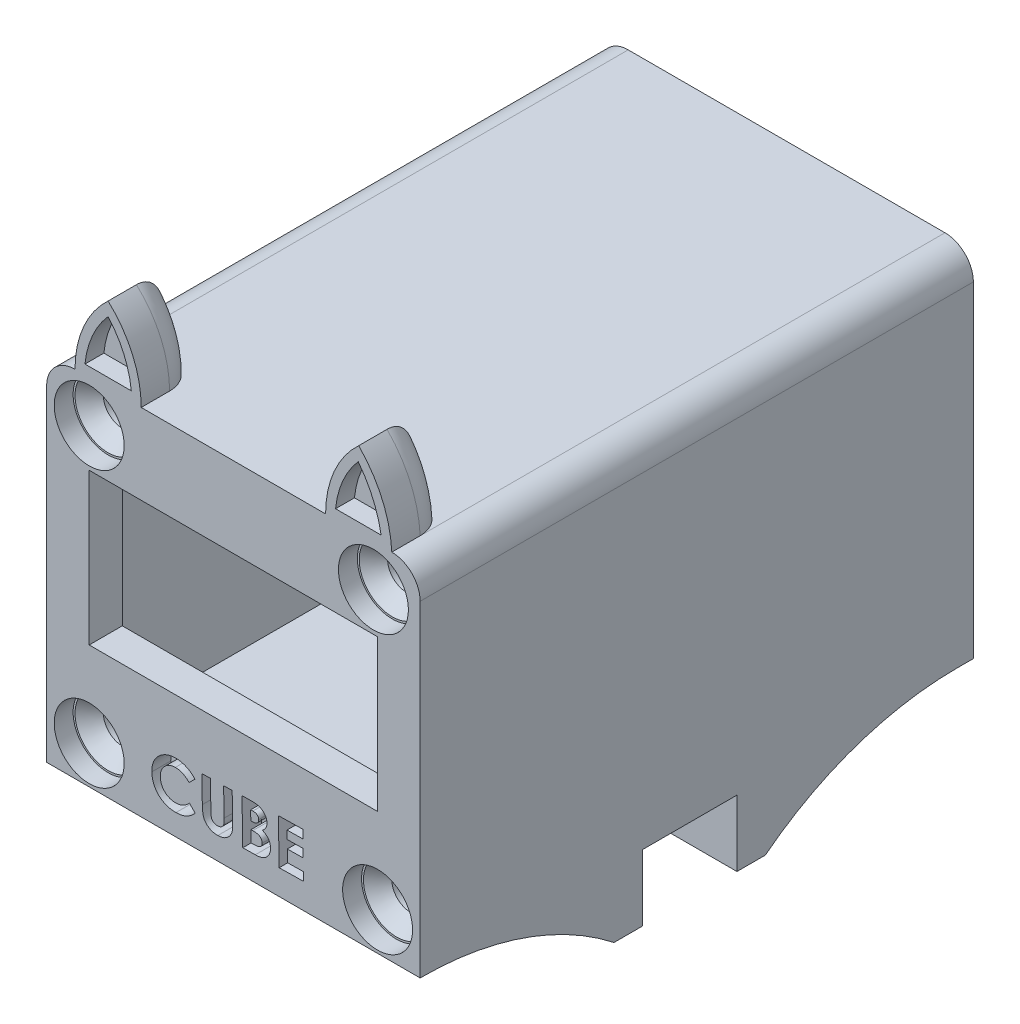
SolidWorks part; units mm, degrees
ref_plane "Plan de face" through (0, 0, 0) normal (0, 0, 1) x (1, 0, 0)
ref_plane "Plan de dessus" through (0, 0, 0) normal (0, 1, 0) x (1, 0, 0)
ref_plane "Plan de droite" through (0, 0, 0) normal (1, 0, 0) x (0, 0, -1)
sketch "Esquisse1" plane through (0, 0, 0) normal (0, 0, 1) x (1, 0, 0)
  line L0 (-17.8827, 11.8632) -> (15.6173, 11.8632)
  line L1 (-20.8827, 8.8632) -> (-20.8827, -25.6368)
  line L2 (18.6173, 8.8632) -> (18.6173, -25.6368)
  line L3 (-20.8827, -25.6368) -> (18.6173, -25.6368)
  line L5 (-16.3827, 3.3632) -> (14.1173, 3.3632)
  line L6 (-16.3827, 3.3632) -> (-16.3827, -12.6368)
  line L7 (-16.3827, -12.6368) -> (14.1173, -12.6368)
  line L8 (14.1173, 3.3632) -> (14.1173, -12.6368)
  arc A0 (18.6173, 8.8632) -> (15.6173, 11.8632) centre (15.6173, 8.8632) ccw
  arc A1 (-20.8827, 8.8632) -> (-17.8827, 11.8632) centre (-17.8827, 8.8632) cw
  point P6 (18.6173, 11.8632)
  point P9 (-20.8827, 11.8632)
  dimension "D3" = 3
  dimension "D1" = 39.5
  dimension "D2" = 37.5
  dimension "D4" = 8.5
  dimension "D5" = 4.5
  dimension "D6" = 16
  dimension "D7" = 4.5
extrude "Boss.-Extru.1" add sketch "Esquisse1" along normal blind 3.5
sketch "Esquisse2" plane through (0, 0, 0) normal (0, 0, -1) x (-1, 0, 0)
  line L8 (-17.1173, 8.8632) -> (-17.1173, -24.1368)
  line L9 (-17.1173, -24.1368) -> (19.3827, -24.1368)
  line L10 (19.3827, -24.1368) -> (19.3827, 8.8632)
  line L11 (17.8827, 10.3632) -> (-15.6173, 10.3632)
  line L12 (-17.1173, 8.8632) -> (-17.1173, -24.1368)
  line L13 (-17.1173, -24.1368) -> (19.3827, -24.1368)
  line L14 (19.3827, -24.1368) -> (19.3827, 8.8632)
  line L15 (17.8827, 10.3632) -> (-15.6173, 10.3632)
  line L20 (-18.6173, 8.8632) -> (-18.6173, -25.6368)
  line L21 (-18.6173, -25.6368) -> (20.8827, -25.6368)
  line L22 (20.8827, -25.6368) -> (20.8827, 8.8632)
  line L23 (17.8827, 11.8632) -> (-15.6173, 11.8632)
  line L24 (-18.6173, 8.8632) -> (-18.6173, -25.6368)
  line L25 (-18.6173, -25.6368) -> (20.8827, -25.6368)
  line L26 (20.8827, -25.6368) -> (20.8827, 8.8632)
  line L27 (17.8827, 11.8632) -> (-15.6173, 11.8632)
  arc A4 (-15.6173, 10.3632) -> (-17.1173, 8.8632) centre (-15.6173, 8.8632) ccw
  arc A5 (19.3827, 8.8632) -> (17.8827, 10.3632) centre (17.8827, 8.8632) ccw
  arc A6 (-15.6173, 10.3632) -> (-17.1173, 8.8632) centre (-15.6173, 8.8632) ccw
  arc A7 (19.3827, 8.8632) -> (17.8827, 10.3632) centre (17.8827, 8.8632) ccw
  arc A10 (-15.6173, 11.8632) -> (-18.6173, 8.8632) centre (-15.6173, 8.8632) ccw
  arc A11 (20.8827, 8.8632) -> (17.8827, 11.8632) centre (17.8827, 8.8632) ccw
  arc A12 (-15.6173, 11.8632) -> (-18.6173, 8.8632) centre (-15.6173, 8.8632) ccw
  arc A13 (20.8827, 8.8632) -> (17.8827, 11.8632) centre (17.8827, 8.8632) ccw
  dimension "D1" = 1.5
  dimension "D2" = 0
extrude "Boss.-Extru.2" add sketch "Esquisse2" along normal blind 55
sketch "Esquisse3" plane through (0, 0, 0) normal (0, 0, -1) x (-1, 0, 0)
  line L0 (-17.1173, -24.1368) -> (19.3827, -24.1368) construction
  line L1 (-17.1173, -24.1368) -> (19.3827, -24.1368)
  line L2 (-17.1173, -24.1368) -> (-17.1173, -19.1368)
  line L3 (-17.1173, -19.1368) -> (19.3827, -19.1368)
  line L4 (19.3827, -24.1368) -> (19.3827, -19.1368)
  line L5 (-17.1173, -24.1368) -> (19.3827, -24.1368) construction
  line L6 (19.3827, -24.1368) -> (19.3827, 8.8632) construction
  line L7 (17.8827, 10.3632) -> (-15.6173, 10.3632) construction
  line L8 (-17.1173, 10.3632) -> (19.3827, 10.3632)
  line L9 (-17.1173, 10.3632) -> (-17.1173, 5.3632)
  line L10 (-17.1173, 5.3632) -> (19.3827, 5.3632)
  line L11 (19.3827, 10.3632) -> (19.3827, 5.3632)
  line L12 (-17.1173, 8.8632) -> (-17.1173, -24.1368) construction
  line L13 (-5.1173, -19.1368) -> (7.3827, -19.1368)
  line L14 (-5.1173, -19.1368) -> (-5.1173, -21.6368)
  line L15 (-5.1173, -21.6368) -> (7.3827, -21.6368)
  line L16 (7.3827, -19.1368) -> (7.3827, -21.6368)
  line L17 (-5.1173, 10.3632) -> (7.3827, 10.3632)
  line L18 (-5.1173, 10.3632) -> (-5.1173, 5.3632)
  line L19 (-5.1173, 5.3632) -> (7.3827, 5.3632)
  line L20 (7.3827, 10.3632) -> (7.3827, 5.3632)
  line M10 (17.8827, 10.3632) -> (-15.6173, 10.3632)
  arc M11 (-15.6173, 10.3632) -> (-17.1173, 8.8632) centre (-15.6173, 8.8632) ccw
  line M12 (-17.1173, 8.8632) -> (-17.1173, -24.1368)
  line M13 (-17.1173, -24.1368) -> (19.3827, -24.1368)
  line M14 (19.3827, -24.1368) -> (19.3827, 8.8632)
  arc M15 (19.3827, 8.8632) -> (17.8827, 10.3632) centre (17.8827, 8.8632) ccw
  dimension "D1" = 5
  dimension "D2" = 0
  dimension "D3" = 5
  dimension "D4" = 2.5
  dimension "D5" = 12
  dimension "D6" = 12
  dimension "D7" = 12
  dimension "D8" = 12
  dimension "D9" = 0
  dimension "D10" = 0
extrude "Boss.-Extru.3" add sketch "Esquisse3" along normal blind 1.5 contours L18 L10 M10 M11 M12 | L20 L10 M10 M14 M15 | L3 L16 L15 L14 M12 M13 M14 region at (-1.1327, -21.8951, 0) region at (11.0713, 7.8456, 0) region at (-13.3367, 7.8456, 0)
fillet "Congé1" radius 2.5 1 edges at (-1.1327, -21.6368, -1.5)
sketch "Esquisse4" plane through (0, 0, 3.5) normal (0, 0, 1) x (1, 0, 0)
  line L0 (-20.8827, 7.4632) -> (18.6173, 7.4632) construction
  line L1 (-20.8827, 8.8632) -> (-20.8827, -25.6368) construction
  line L2 (18.6173, -25.6368) -> (18.6173, 8.8632) construction
  line L4 (-20.8827, -25.6368) -> (18.6173, -25.6368) construction
  line L5 (14.1173, -25.6368) -> (14.1173, 11.8632) construction
  line L6 (15.6173, 11.8632) -> (-17.8827, 11.8632) construction
  line L8 (-16.3827, -25.6368) -> (-16.3827, 11.8632) construction
  line L10 (-20.8827, -21.6368) -> (18.6173, -21.6368) construction
  circle A0 centre (-16.3827, 7.4632) radius 2
  circle A1 centre (13.6721, 7.4632) radius 2
  circle A2 centre (14.1173, -21.6368) radius 2
  circle A3 centre (-16.3827, -21.6368) radius 2
  point P6 (-16.3827, 7.4632)
  point P17 (13.6721, 7.4632)
  point P18 (14.1173, -21.6368)
  point P19 (-16.3827, -21.6368)
  dimension "D5" = 4
  dimension "D6" = 4
  dimension "D7" = 4
  dimension "D8" = 4
  dimension "D1" = 4
  dimension "D2" = 4.5
  dimension "D3" = 4.4
  dimension "D4" = 4.5
extrude "Enlèv. mat.-Extru.1" cut sketch "Esquisse4" against normal blind 9.5
sketch "Esquisse5" plane through (0, 0, 3.5) normal (0, 0, 1) x (1, 0, 0)
  line L0 (-15.5568, -23.4583) -> (12.4785, -22.7833) construction
  circle A0 centre (-16.3827, -21.6368) radius 3.7
  circle A1 centre (13.6721, 7.4632) radius 3.7
  circle A2 centre (-16.3827, 7.4632) radius 3.7
  circle A3 centre (14.1173, -21.6368) radius 3.7
  circle A4 centre (-16.3827, -21.6368) radius 2 construction
  circle A5 centre (14.1173, -21.6368) radius 2 construction
  text T0 "<b>CUBE</b>" font "Century Gothic" height in points 18
  dimension "D1" = 7.4
  dimension "D2" = 7.4
  dimension "D3" = 7.4
  dimension "D4" = 7.4
extrude "Enlèv. mat.-Extru.5" cut sketch "Esquisse5" against normal blind 2
sketch "Esquisse6" plane through (0, 0, -55) normal (0, 0, -1) x (-1, 0, 0)
  line L0 (1.1327, 10.3632) -> (1.1327, -24.1368) construction
  line L1 (7.3827, 10.3632) -> (-5.1173, 10.3632) construction
  line L2 (-17.1173, -24.1368) -> (19.3827, -24.1368) construction
  line L3 (-2.6173, 8.1132) -> (-2.6173, 10.3632)
  line L4 (17.8827, 10.3632) -> (-15.6173, 10.3632) construction
  line L5 (-2.6173, 10.3632) -> (-2.6173, 11.8632)
  line L6 (4.8827, 8.1132) -> (4.8827, 10.3632)
  line L7 (1.1327, -6.8868) -> (9.6914, -6.8868) construction
  line L8 (4.8827, -21.8868) -> (4.8827, -24.1368)
  line L9 (-2.6173, -24.1368) -> (4.8827, -24.1368)
  line L10 (-2.6173, -21.8868) -> (-2.6173, -24.1368)
  line L11 (17.8827, 11.8632) -> (-15.6173, 11.8632) construction
  line L12 (-2.6173, 11.8632) -> (4.8827, 11.8632)
  line L13 (4.8827, 11.8632) -> (4.8827, 10.3632)
  line L14 (4.8827, -24.1368) -> (4.8827, -25.6368)
  line L15 (-18.6173, -25.6368) -> (20.8827, -25.6368) construction
  line L16 (4.8827, -25.6368) -> (-2.6173, -25.6368)
  line L17 (-2.6173, -25.6368) -> (-2.6173, -24.1368)
  circle A0 centre (1.1327, 8.1132) radius 2.25
  circle A1 centre (1.1327, 8.1132) radius 3.75
  circle A2 centre (1.1327, -21.8868) radius 3.75
  circle A3 centre (1.1327, -21.8868) radius 2.25
  point P31 (1.1327, 11.8632)
  line M6 (-18.6173, -25.6368) -> (20.8827, -25.6368)
  line M9 (17.8827, 11.8632) -> (-15.6173, 11.8632)
  line M12 (-15.6173, 10.3632) -> (17.8827, 10.3632)
  line M15 (19.3827, -24.1368) -> (-17.1173, -24.1368)
  dimension "D1" = 4.5
  dimension "D2" = 3.75
extrude "Boss.-Extru.5" add sketch "Esquisse6" against normal blind 7 contours A2 L10 M15 | A2 L17 M6 M15 | A2 L16 L14 M15 | A2 L9 M15 | L8 A2 M15 | A3 L9 A2 M15 | A1 A0 M12 | A1 L12 L5 M12 | A1 L3 M12 | A1 M12 | A1 L13 M12 M9 | A1 L6 M12 region at (2.3337, 9.2686, -55) region at (2.3968, 9.8125, -55) region at (1.6458, 11.2886, -55) region at (-4.6622, 9.8125, -55) region at (-1.1327, 10.9748, -55) region at (-3.9112, 11.2886, -55) region at (-4.5991, -23.0423, -55) region at (-4.6622, -23.5862, -55) region at (-3.9112, -25.0623, -55) region at (2.3968, -23.5862, -55) region at (-1.1327, -24.7485, -55) region at (1.6458, -25.0623, -55)
sketch "Esquisse7" plane through (0, 0, -55) normal (0, 0, -1) x (-1, 0, 0)
  line L0 (7.3827, 10.3632) -> (-5.1173, 10.3632) construction
  line L1 (-3.1173, 10.3632) -> (5.3827, 10.3632)
  line L2 (-3.1173, 10.3632) -> (-3.1173, 8.1132)
  line L3 (-3.1173, 8.1132) -> (5.3827, 8.1132)
  line L4 (5.3827, 10.3632) -> (5.3827, 8.1132)
  line L5 (-2.6173, 8.1132) -> (-2.6173, 10.3632) construction
  line L6 (4.8827, 8.1132) -> (4.8827, 10.3632) construction
  arc A0 (-3.1173, 8.1132) -> (5.3827, 8.1132) centre (1.1327, 8.1132) ccw
  arc A1 (4.8827, 8.1132) -> (-2.6173, 8.1132) centre (1.1327, 8.1132) cw
  line M13 (4.8827, 8.1132) -> (4.8827, 10.3632)
  line M14 (4.8827, 10.3632) -> (17.8827, 10.3632)
  line M24 (-15.6173, 10.3632) -> (-2.6173, 10.3632)
  line M25 (-2.6173, 10.3632) -> (-2.6173, 8.1132)
  arc M26 (-2.6173, 8.1132) -> (4.8827, 8.1132) centre (1.1327, 8.1132) ccw
  dimension "D1" = 2.25
  dimension "D2" = 0.5
  dimension "D3" = 0.5
extrude "Boss.-Extru.6" add sketch "Esquisse7" against normal blind 7 contours L3 A0 M26 | L4 L3 M14 M13 | L2 L3 M25 M24 region at (2.8673, 9.2382, -55) region at (2.8673, 8.0181, -55) region at (-5.1327, 9.2382, -55)
chamfer "Chanfrein1" distance 1.5 angle 45 4 edges at (-14.3827, -21.6368, 1.5) (-14.3827, 7.4632, 1.5) (15.6721, 7.4632, 1.5) (16.1173, -21.6368, 1.5)
sketch "Esquisse8" plane through (0, 0, 0) normal (0, 0, -1) x (-1, 0, 0)
  line L0 (7.3827, 10.3632) -> (7.3827, 5.3632) construction
  line L1 (-5.1173, 5.3632) -> (7.3827, 5.3632)
  line L2 (-5.1173, 5.3632) -> (-5.1173, 10.3632)
  line L3 (-5.1173, 10.3632) -> (7.3827, 10.3632)
  line L4 (7.3827, 5.3632) -> (7.3827, 10.3632)
  line L5 (7.3827, 10.3632) -> (7.3827, 5.3632) construction
extrude "Enlèv. mat.-Extru.6" cut sketch "Esquisse8" against normal blind 2
sketch "Esquisse10" plane through (0, 0, 3.5) normal (0, 0, 1) x (1, 0, 0)
  line L0 (-17.8827, 11.8632) -> (15.6173, 11.8632)
  line L1 (15.6173, 11.8632) -> (-17.8827, 11.8632) construction
  line L2 (-14.3827, 11.8632) -> (-14.3827, 19.8632) construction
  line L3 (-14.3827, 19.8632) -> (12.1173, 19.8632) construction
  line L4 (12.1173, 19.8632) -> (12.1173, 11.8632) construction
  line L5 (-14.3827, 11.8632) -> (-10.8827, 11.8632) construction
  line L6 (12.1173, 11.8632) -> (8.6173, 11.8632) construction
  arc A0 (18.6173, 8.8632) -> (15.6173, 11.8632) centre (15.6173, 8.8632) ccw construction
  arc A1 (-17.8827, 11.8632) -> (-14.3827, 19.8632) centre (-6.9898, 11.8632) cw
  arc A2 (-10.8827, 11.8632) -> (-14.3827, 19.8632) centre (-21.7756, 11.8632) ccw
  arc A3 (8.6173, 11.8632) -> (12.1173, 19.8632) centre (19.5102, 11.8632) cw
  arc A4 (12.1173, 19.8632) -> (15.6173, 11.8632) centre (3.4155, 11.2905) cw
  dimension "D1" = 3.5
  dimension "D2" = 3.5
  dimension "D3" = 8
  dimension "D4" = 3.5
  dimension "D5" = 3.5
extrude "Boss.-Extru.7" add sketch "Esquisse10" against normal blind 6 contours A4 A3 L0 | L0 A2 A1 region at (-14.3827, 14.9398, 3.5) region at (12.0777, 14.9199, 3.5)
fillet "Congé2" radius 3 4 edges at (14.6066, 16.1866, -2.5) (9.5306, 16.2292, -2.5) (-11.796, 16.2292, -2.5) (-16.9694, 16.2292, -2.5)
sketch "Esquisse12" plane through (0, 0, 3.5) normal (0, 0, 1) x (1, 0, 0)
  line L0 (-17.8827, 11.8632) -> (-10.8827, 11.8632)
  line L1 (8.6173, 11.8632) -> (15.6173, 11.8632)
  line L2 (-16.832, 12.8632) -> (-11.9334, 12.8632)
  line L3 (9.668, 12.8632) -> (14.4871, 12.8632)
  arc A0 (-17.8827, 11.8632) -> (-14.3827, 19.8632) centre (-6.9898, 11.8632) cw
  arc A1 (-10.8827, 11.8632) -> (-14.3827, 19.8632) centre (-21.7756, 11.8632) ccw
  arc A2 (8.6173, 11.8632) -> (12.1173, 19.8632) centre (19.5102, 11.8632) cw
  arc A3 (12.1173, 19.8632) -> (15.6173, 11.8632) centre (2.3237, 10.8128) cw
  arc A4 (-11.9334, 12.8632) -> (-14.3827, 18.4369) centre (-21.7756, 11.8632) ccw
  arc A5 (-16.832, 12.8632) -> (-14.3827, 18.4369) centre (-6.9898, 11.8632) cw
  arc A6 (12.0659, 18.3787) -> (14.4871, 12.8632) centre (2.3237, 10.8128) cw
  arc A7 (9.668, 12.8632) -> (12.0659, 18.3787) centre (19.5102, 11.8632) cw
  dimension "D1" = 1
extrude "Enlèv. mat.-Extru.7" cut sketch "Esquisse12" against normal blind 2 contours L2 A4 A5 | L3 A6 A7
sketch "Esquisse13" plane through (0, -25.6368, 0) normal (0, -1, 0) x (1, 0, 0)
  line L0 (-20.8827, 3.5) -> (-20.8827, -55) construction
  line L1 (-20.8827, -17) -> (18.6173, -17)
  line L2 (-20.8827, -17) -> (-20.8827, -20)
  line L3 (-20.8827, -20) -> (18.6173, -20)
  line L4 (18.6173, -17) -> (18.6173, -20)
  line L5 (18.6173, 3.5) -> (18.6173, -55) construction
  line L6 (18.6173, -55) -> (-20.8827, -55) construction
  line L7 (18.6173, -30) -> (-20.8827, -30)
  line L8 (18.6173, -30) -> (18.6173, -33)
  line L9 (18.6173, -33) -> (-20.8827, -33)
  line L10 (-20.8827, -30) -> (-20.8827, -33)
  dimension "D1" = 3
  dimension "D2" = 3
  dimension "D3" = 10
  dimension "D4" = 22
extrude "Boss.-Extru.8" add sketch "Esquisse13" along normal blind 7
fillet "Congé3" radius 33 2 edges at (-1.1327, -25.6368, -33) (-1.1327, -25.6368, -17)
